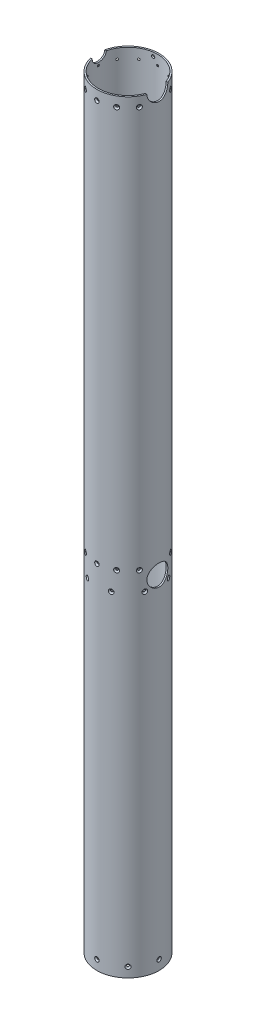
SolidWorks part; units mm, degrees
material "6063-T6"
ref_plane "Front Plane" through (0, 0, 0) normal (0, 0, 1) x (1, 0, 0)
ref_plane "Top Plane" through (0, 0, 0) normal (0, 1, 0) x (1, 0, 0)
ref_plane "Right Plane" through (0, 0, 0) normal (1, 0, 0) x (0, 0, -1)
sketch "Sketch1" plane through (0, 0, 0) normal (0, 1, 0) x (1, 0, 0)
  circle A0 centre (0, 0) radius 24.1554
  circle A1 centre (0, 0) radius 25.4
  dimension "D1" = 50.8
  dimension "D2" = 1.2446
extrude "body" add sketch "Sketch1" along normal blind 622.3
hole_wizard "M2x0.4 Tapped Hole1" positions "3DSketch1" profile "Sketch2" tap size "M2x0.4" standard "ANSI Metric"
sketch3d "3DSketch1"
  line L0 (25.4, 7.9375, 0) -> (-1.0246, 7.9375, 0)
  point P0 (25.4, 7.9375, 0)
sketch "Sketch2" plane through (25.4, 7.9375, 0) normal (0, 1, 0) x (0, 0, -1)
  line L0 (0, 0) -> (0, 8.3547)
  line L1 (0, 8.3547) -> (0.8, 7.874)
  line L2 (0.8, 7.874) -> (0.8, 1.09)
  line L3 (0.8, 1.09) -> (1.89, 0)
  line L4 (1.89, 0) -> (0, 0)
  line L5 (-0.8, 1.09) -> (-1.89, 0) construction
  line L6 (0, 8.3547) -> (-0.8, 7.874) construction
  line L7 (0, -6.35) -> (0, 107.95) construction
  dimension "Tap Drill Dia." = 1.6
  dimension "Tap Drill Depth" = 7.874
  dimension "Near C'Sink Dia." = 3.78
  dimension "Near C'Sink Angle" = 90
  dimension "Drill Angle" = 118
cosmetic thread "Hole Thread1"
pattern_circular "CirPattern1" count 8 over 360 about axis through (0, 0, 0) along (0, 1, 0) of "M2x0.4 Tapped Hole1"
cosmetic thread "Hole Thread2"
cosmetic thread "Hole Thread3"
cosmetic thread "Hole Thread4"
cosmetic thread "Hole Thread5"
cosmetic thread "Hole Thread6"
cosmetic thread "Hole Thread7"
cosmetic thread "Hole Thread8"
hole_wizard "M2x0.4 Tapped Hole2" positions "3DSketch2" profile "Sketch3" tap size "M2x0.4" standard "ANSI Metric"
sketch3d "3DSketch2"
  line L0 (23.4665, 271.4625, 9.7202) -> (2.1339, 271.4625, 0.8839)
  point P0 (23.4665, 271.4625, 9.7202)
sketch "Sketch3" plane through (23.4665, 271.4625, 9.7202) normal (0, 1, 0) x (0.3827, 0, -0.9239)
  line L0 (0, 0) -> (0, 8.3547)
  line L1 (0, 8.3547) -> (0.8, 7.874)
  line L2 (0.8, 7.874) -> (0.8, 1.09)
  line L3 (0.8, 1.09) -> (1.89, 0)
  line L4 (1.89, 0) -> (0, 0)
  line L5 (-0.8, 1.09) -> (-1.89, 0) construction
  line L6 (0, 8.3547) -> (-0.8, 7.874) construction
  line L7 (0, -6.35) -> (0, 107.95) construction
  dimension "Tap Drill Dia." = 1.6
  dimension "Tap Drill Depth" = 7.874
  dimension "Near C'Sink Dia." = 3.78
  dimension "Near C'Sink Angle" = 90
  dimension "Drill Angle" = 118
cosmetic thread "Hole Thread9"
pattern_circular "CirPattern2" count 8 over 360 about axis through (0, 622.3, 0) along (0, -1, 0) of "M2x0.4 Tapped Hole2" reverse direction yes
cosmetic thread "Hole Thread10"
cosmetic thread "Hole Thread11"
cosmetic thread "Hole Thread12"
cosmetic thread "Hole Thread13"
cosmetic thread "Hole Thread14"
cosmetic thread "Hole Thread15"
cosmetic thread "Hole Thread16"
hole_wizard "M2x0.4 Tapped Hole3" positions "3DSketch3" profile "Sketch4" tap size "M2x0.4" standard "ANSI Metric"
sketch3d "3DSketch3"
  line L0 (0, 614.3498, 25.4) -> (0, 614.3498, 15.3774)
  point P0 (0, 614.3498, 25.4)
sketch "Sketch4" plane through (0, 614.3498, 25.4) normal (1, 0, 0) x (0, -1, 0)
  line L0 (0, 0) -> (0, 8.3547)
  line L1 (0, 8.3547) -> (0.8, 7.874)
  line L2 (0.8, 7.874) -> (0.8, 1.09)
  line L3 (0.8, 1.09) -> (1.89, 0)
  line L4 (1.89, 0) -> (0, 0)
  line L5 (-0.8, 1.09) -> (-1.89, 0) construction
  line L6 (0, 8.3547) -> (-0.8, 7.874) construction
  line L7 (0, -6.35) -> (0, 107.95) construction
  dimension "Tap Drill Dia." = 1.6
  dimension "Tap Drill Depth" = 7.874
  dimension "Near C'Sink Dia." = 3.78
  dimension "Near C'Sink Angle" = 90
  dimension "Drill Angle" = 118
cosmetic thread "Hole Thread17"
pattern_circular "CirPattern3" count 12 over 360 about axis through (0, 622.3, 0) along (0, -1, 0) skipping 9 of "M2x0.4 Tapped Hole3"
cosmetic thread "Hole Thread18"
cosmetic thread "Hole Thread19"
cosmetic thread "Hole Thread20"
cosmetic thread "Hole Thread21"
cosmetic thread "Hole Thread22"
cosmetic thread "Hole Thread23"
cosmetic thread "Hole Thread24"
cosmetic thread "Hole Thread25"
cosmetic thread "Hole Thread26"
cosmetic thread "Hole Thread27"
hole_wizard "M2x0.4 Tapped Hole4" positions "3DSketch4" profile "Sketch5" tap size "M2x0.4" standard "ANSI Metric"
sketch3d "3DSketch4"
  line L0 (-25.4, 287.3502, 0) -> (-18.8369, 287.3502, 0)
  point P0 (-25.4, 287.3502, 0)
sketch "Sketch5" plane through (-25.4, 287.3502, 0) normal (0, 1, 0) x (0, 0, 1)
  line L0 (0, 0) -> (0, 8.3547)
  line L1 (0, 8.3547) -> (0.8, 7.874)
  line L2 (0.8, 7.874) -> (0.8, 1.09)
  line L3 (0.8, 1.09) -> (1.89, 0)
  line L4 (1.89, 0) -> (0, 0)
  line L5 (-0.8, 1.09) -> (-1.89, 0) construction
  line L6 (0, 8.3547) -> (-0.8, 7.874) construction
  line L7 (0, -6.35) -> (0, 107.95) construction
  dimension "Tap Drill Dia." = 1.6
  dimension "Tap Drill Depth" = 7.874
  dimension "Near C'Sink Dia." = 3.78
  dimension "Near C'Sink Angle" = 90
  dimension "Drill Angle" = 118
cosmetic thread "Hole Thread28"
pattern_circular "CirPattern4" count 12 over 360 about axis through (0, 622.3, 0) along (0, -1, 0) skipping 6 of "M2x0.4 Tapped Hole4" reverse direction yes
cosmetic thread "Hole Thread29"
cosmetic thread "Hole Thread30"
cosmetic thread "Hole Thread31"
cosmetic thread "Hole Thread32"
cosmetic thread "Hole Thread33"
cosmetic thread "Hole Thread34"
cosmetic thread "Hole Thread35"
cosmetic thread "Hole Thread36"
cosmetic thread "Hole Thread37"
cosmetic thread "Hole Thread38"
hole_wizard "43/64 (0.67188) Diameter Hole1" positions "3DSketch5" profile "Sketch6" hole size "43/64" standard "ANSI Inch"
sketch3d "3DSketch5"
  line L0 (25.4, 279.4, 0) -> (13.4323, 279.4, 0)
  point P0 (25.4, 279.4, 0)
  point P5 (25.4, 622.3, 0)
sketch "Sketch6" plane through (25.4, 279.4, 0) normal (0, 1, 0) x (0, 0, -1)
  line L0 (0, 0) -> (0, 33.8291)
  line L1 (0, 33.8291) -> (8.5329, 28.702)
  line L2 (8.5329, 28.702) -> (8.5329, 0)
  line L3 (8.5329, 0) -> (0, 0)
  line L4 (0, 33.8291) -> (-8.5329, 28.702) construction
  line L5 (0, -6.35) -> (0, 107.95) construction
  dimension "Hole Dia." = 17.0658
  dimension "Hole Depth" = 28.702
  dimension "Drill Angle" = 118
pattern_linear "LPattern1" [suppressed] of bodies 110
hole_wizard "7/16 Clearance Hole1" positions "3DSketch6" profile "Sketch7" hole size "7/16" standard "ANSI Inch"
sketch3d "3DSketch6"
  line L0 (-25.4, 279.4, 0) -> (-8.764, 279.4, 0)
  point P0 (-25.4, 279.4, 0)
  point P15 (-25.4, 622.3, 0)
sketch "Sketch7" plane through (-25.4, 279.4, 0) normal (0, 1, 0) x (0, 0, 1)
  line L0 (0, 0) -> (0, 32.1596)
  line L1 (0, 32.1596) -> (5.7544, 28.702)
  line L2 (5.7544, 28.702) -> (5.7544, 0)
  line L3 (5.7544, 0) -> (0, 0)
  line L4 (0, 32.1596) -> (-5.7544, 28.702) construction
  line L5 (0, -6.35) -> (0, 107.95) construction
  dimension "Hole Dia." = 11.5087
  dimension "Hole Depth" = 28.702
  dimension "Drill Angle" = 118
hole_wizard "3/32 (0.09375) Diameter Hole1" positions "Sketch8" profile "Sketch9" hole size "3/32" standard "ANSI Inch"
sketch "Sketch8" plane through (0, 0, -25.4) normal (0, 0, -1) x (-1, 0, 0)
  point P0 (3.4131, 619.125)
sketch "Sketch9" plane through (-3.4131, 619.125, -25.4) normal (1, 0, 0) x (0, 1, 0)
  line L0 (0, 0) -> (0, 30.6795)
  line L1 (0, 30.6795) -> (1.1906, 29.9641)
  line L2 (1.1906, 29.9641) -> (1.1906, 0)
  line L3 (1.1906, 0) -> (0, 0)
  line L4 (0, 30.6795) -> (-1.1906, 29.9641) construction
  line L5 (0, -6.35) -> (0, 107.95) construction
  dimension "Hole Dia." = 2.3812
  dimension "Hole Depth" = 29.9641
  dimension "Drill Angle" = 118
